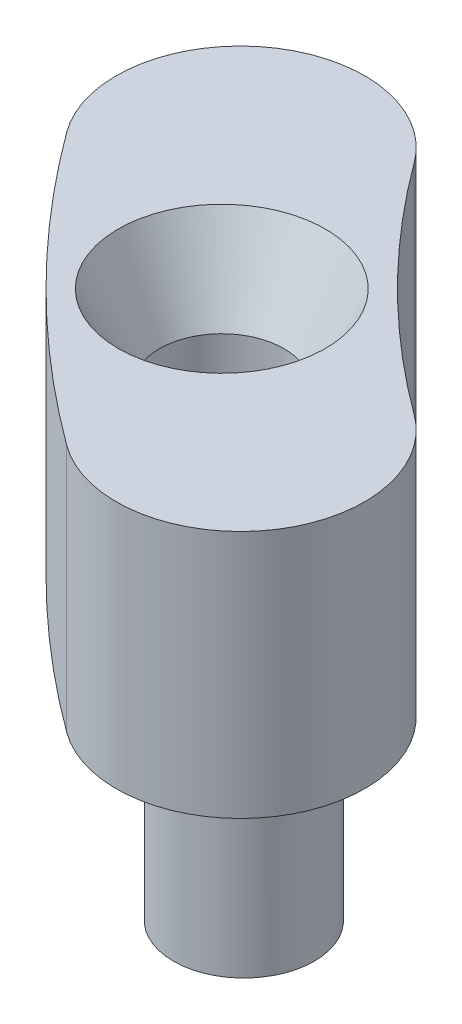
SolidWorks part; units mm, degrees
material "6061 合金"
ref_plane "前视基准面" through (0, 0, 0) normal (0, 0, 1) x (1, 0, 0)
ref_plane "上视基准面" through (0, 0, 0) normal (0, 1, 0) x (1, 0, 0)
ref_plane "右视基准面" through (0, 0, 0) normal (1, 0, 0) x (0, 0, -1)
other "Configuration Table"
sketch "草图1" plane through (0, 0, 0) normal (0, 1, 0) x (1, 0, 0)
  line L0 (-30, 0) -> (30, 0) construction
  line L1 (0, 0) -> (-25.9808, -15) construction
  line L2 (0, 0) -> (0, -30) construction
  line L3 (0, 0) -> (-15, -25.9808) construction
  line L4 (0, 0) -> (-21.5668, -21.5668) construction
  circle A0 centre (0, 0) radius 27.5 construction
  arc A1 (-24.5925, -18.0405) -> (-18.0405, -24.5925) centre (0, 0) ccw
  arc A2 (-19.7546, -14.4915) -> (-14.4915, -19.7546) centre (0, 0) ccw
  circle A3 centre (-19.4454, -19.4454) radius 1.5
  arc A4 (-19.7546, -14.4915) -> (-24.5925, -18.0405) centre (-22.1736, -16.266) ccw
  arc A5 (-14.4915, -19.7546) -> (-18.0405, -24.5925) centre (-16.266, -22.1736) cw
  dimension "D1" = 55
  dimension "D2" = 61
  dimension "D3" = 49
  dimension "D7" = 3
  dimension "D4" = 30
  dimension "D5" = 30
  dimension "D6" = 45
extrude "凸台-拉伸1" add sketch "草图1" along normal blind 6
ref_axis "基准轴1" through (-19.4454, 6, 19.4454) along (0, -1, 0)
ref_plane "基准面2" through (-19.4454, 0, 0) normal (1, 0, 0) x (0, 0, -1)
sketch "草图2" plane through (-19.4454, 0, 0) normal (1, 0, 0) x (0, 0, -1)
  line L0 (-19.4454, 6) -> (-19.4454, 0) construction
  line L1 (-19.4454, 6) -> (-19.4454, 0) construction
  line L3 (-19.4454, 6) -> (-21.9454, 6)
  line L4 (-19.7546, 6) -> (-25.1736, 6) construction
  line L5 (-21.9454, 6) -> (-20.6954, 3.5)
  line L6 (-20.6954, 3.5) -> (-19.4454, 3.5)
  line L7 (-19.4454, 6) -> (-19.4454, 3.5)
  dimension "D1" = 5
  dimension "D2" = 2.5
  dimension "D3" = 2.5
revolve "切除-旋转1" cut sketch "草图2" angle 360 about L0
sketch "草图3" plane through (0, 0, 0) normal (0, -1, 0) x (1, 0, 0)
  line L0 (-19.4454, 19.4454) -> (0, 0) construction
  line L1 (-15.9693, 22.3882) -> (0, 0) construction
  line L2 (-22.3882, 15.9693) -> (0, 0) construction
  circle A0 centre (0, 0) radius 27.5 construction
  circle A1 centre (-15.9693, 22.3882) radius 1.7
  circle A2 centre (-22.3882, 15.9693) radius 2
  dimension "D2" = 3.4
  dimension "D4" = 4
  dimension "D1" = 9.5
  dimension "D3" = 9.5
extrude "凸台-拉伸2" add sketch "草图3" along normal blind 4
